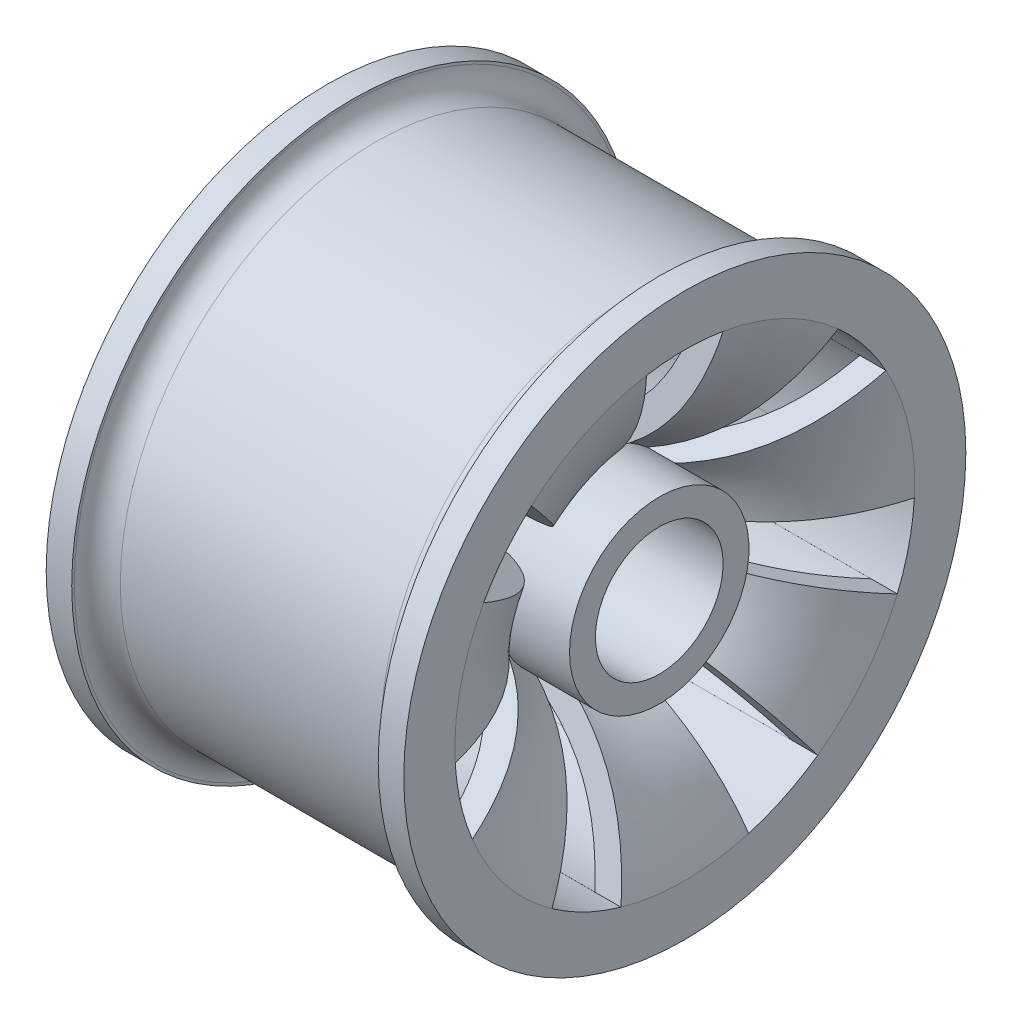
SolidWorks part; units mm, degrees
ref_plane "Front Plane" through (0, 0, 0) normal (0, 0, 1) x (1, 0, 0)
ref_plane "Top Plane" through (0, 0, 0) normal (0, 1, 0) x (1, 0, 0)
ref_plane "Right Plane" through (0, 0, 0) normal (1, 0, 0) x (0, 0, -1)
sketch "Sketch2" plane through (0, 0, 0) normal (0, 0, 1) x (1, 0, 0)
sketch "Sketch1" plane through (0, 0, 0) normal (0, 0, 1) x (1, 0, 0)
  line L0 (0, 0) -> (0, 12.5106) construction
  line L1 (0, 0) -> (16.972, 0) construction
  line L2 (-5.9773, 9) -> (5.9773, 9)
  line L3 (7, 9.0024) -> (7, 11.0024)
  line L4 (7, 11.0024) -> (6, 11.0024)
  line L5 (6, 11.0024) -> (6, 10.9)
  line L6 (5.1, 10) -> (-5.1, 10)
  line L7 (0, 2.5) -> (0, 3.5129)
  line L8 (-7, 11.0024) -> (-6, 11.0024)
  line L9 (-7, 9.0024) -> (-7, 11.0024)
  line L10 (-7, 9.0024) -> (-5.9773, 9)
  line L11 (-6, 10.9) -> (-6, 11.0024)
  arc A0 (5.1, 10) -> (6, 10.9) centre (5.1, 10.9) ccw
  arc A1 (-5.1, 10) -> (-6, 10.9) centre (-5.1, 10.9) cw
  spline S0 degree 2 poles (7, 9.0024) (5.8712, 3.4096) (0, 2.5) knots 0 0 0 1 1 1
  spline S1 degree 1 poles (6.0198, 9.2003) (-0.1531, 3.4882) knots 0 0 1 1 construction
  spline S2 degree 2 poles (6.0198, 9.2003) (6.0147, 9.175) (5.9988, 9.0999) (5.9775, 8.9997) (5.5621, 7.215) (4.0693, 5.2526) (1.9351, 3.8551) (0.0001, 3.5128) (-0.0956, 3.4975) (-0.1531, 3.4882) knots 0 0 0 0.004945 0.014834 0.024723 0.375 0.625 0.982243 0.989346 1 1 1 only from (5.9773, 9) to (0, 3.5129)
  point P18 (0, 9)
  point P21 (0, 10)
  dimension "D6" = 0.9
  dimension "D1" = 7
  dimension "D2" = 2
  dimension "D3" = 1
  dimension "D4" = 1
  dimension "D5" = 10
  dimension "D7" = 2.5
  dimension "D8" = 5
  dimension "D9" = 1
revolve "Revolve1" add sketch "Sketch1" angle 360 about L1
sketch "Sketch3" plane through (-7, 0, 0) normal (-1, 0, 0) x (0, 0, 1)
  circle A0 centre (0, 0) radius 3.5129 construction
  circle A1 centre (0, 0) radius 3.5129
  circle A2 centre (0, 0) radius 2.5 construction
  circle A3 centre (0, 0) radius 2.5
extrude "Boss-Extrude3" add sketch "Sketch3" against normal blind 13
sketch "Sketch5" plane through (7, 0, 0) normal (1, 0, 0) x (0, 0, -1)
  line L0 (-0.5853, 3.4638) -> (-1.5, 8.8766)
  line L1 (0.5853, 3.4638) -> (1.5, 8.8766)
  line L2 (3.0731, 1.702) -> (7.8752, 4.3617)
  line L3 (2.3432, 2.6173) -> (6.0048, 6.7072)
  line L4 (3.2467, -1.3414) -> (8.3202, -3.4376)
  line L5 (3.5072, -0.2001) -> (8.9878, -0.5128)
  line L6 (0.9755, -3.3748) -> (2.4999, -8.6483)
  line L7 (2.0303, -2.8668) -> (5.2029, -7.3467)
  line L8 (-2.0303, -2.8668) -> (-5.2029, -7.3467)
  line L9 (-0.9755, -3.3748) -> (-2.4999, -8.6483)
  line L10 (-3.5072, -0.2001) -> (-8.9878, -0.5128)
  line L11 (-3.2467, -1.3414) -> (-8.3202, -3.4376)
  line L12 (-2.3432, 2.6173) -> (-6.0048, 6.7072)
  line L13 (-3.0731, 1.702) -> (-7.8752, 4.3617)
  circle A0 centre (0, 0) radius 2.5 construction
  circle A1 centre (0, 0) radius 2.5
  circle A2 centre (0, 0) radius 3.5129 construction
  circle A3 centre (0, 0) radius 3.5129
  circle A4 centre (0, 0) radius 9.0024 construction
  arc A5 (-0.5853, 3.4638) -> (0.5853, 3.4638) centre (0, 0) cw
  arc A6 (-1.5, 8.8766) -> (1.5, 8.8766) centre (0, 0) cw
  arc A7 (6.0048, 6.7072) -> (7.8752, 4.3617) centre (0, 0) cw
  arc A8 (2.3432, 2.6173) -> (3.0731, 1.702) centre (0, 0) cw
  arc A9 (8.9878, -0.5128) -> (8.3202, -3.4376) centre (0, 0) cw
  arc A10 (3.5072, -0.2001) -> (3.2467, -1.3414) centre (0, 0) cw
  arc A11 (5.2029, -7.3467) -> (2.4999, -8.6483) centre (0, 0) cw
  arc A12 (2.0303, -2.8668) -> (0.9755, -3.3748) centre (0, 0) cw
  arc A13 (-2.4999, -8.6483) -> (-5.2029, -7.3467) centre (0, 0) cw
  arc A14 (-0.9755, -3.3748) -> (-2.0303, -2.8668) centre (0, 0) cw
  arc A15 (-8.3202, -3.4376) -> (-8.9878, -0.5128) centre (0, 0) cw
  arc A16 (-3.2467, -1.3414) -> (-3.5072, -0.2001) centre (0, 0) cw
  arc A17 (-7.8752, 4.3617) -> (-6.0048, 6.7072) centre (0, 0) cw
  arc A18 (-3.0731, 1.702) -> (-2.3432, 2.6173) centre (0, 0) cw
  point P40 (0, 0)
  dimension "D1" = 3
  dimension "D3" = 7
extrude "Cut-Extrude9" cut sketch "Sketch5" against normal through all contours A1 | A3 L12 L3 L13 | A3 L1 L3 L0 | A3 L2 L3 | A3 L4 L3 L5 | A3 L6 L3 L7 | A3 L8 L3 L9 | A3 L10 L3 L11 region at (7, 6.6279, 0) region at (7, 4.1324, 5.1819) region at (7, 4.1324, -5.1819) region at (7, -1.4749, 6.4617) region at (7, -1.4749, -6.4617) region at (7, -5.9716, 2.8757) region at (7, -5.9716, -2.8757) region at (7, 0, 0)
sketch "Sketch6" plane through (0, 0, 0) normal (1, 0, 0) x (0, 0, -1)
  line L0 (0, 11.0024) -> (0, 0) construction
  circle A0 centre (0, 0) radius 11.0024 construction
  circle A1 centre (0, 0) radius 2.5 construction
  circle A2 centre (0, 0) radius 3.5129 construction
  circle A3 centre (0, 0) radius 10 construction
